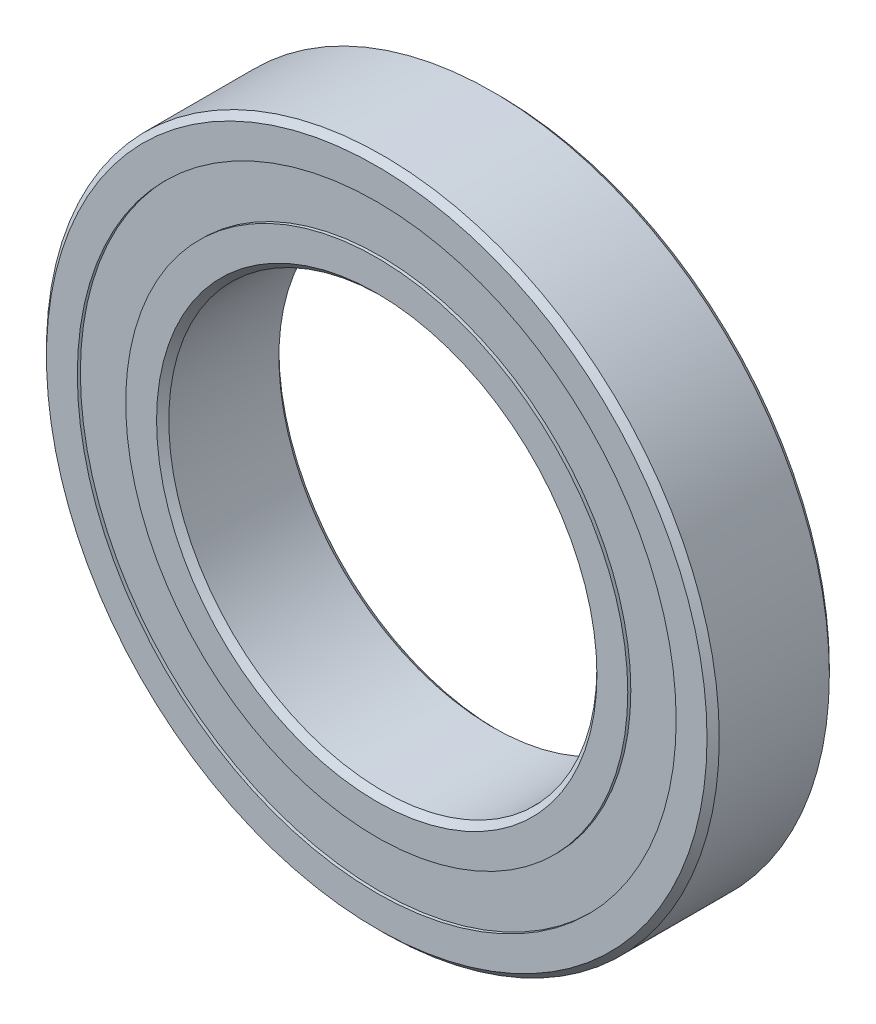
SolidWorks part; units mm, degrees
ref_plane "Front Plane" through (0, 0, 0) normal (0, 0, 1) x (1, 0, 0)
ref_plane "Top Plane" through (0, 0, 0) normal (0, 1, 0) x (1, 0, 0)
ref_plane "Right Plane" through (0, 0, 0) normal (1, 0, 0) x (0, 0, -1)
sketch "Sketch1" plane through (0, 0, 0) normal (1, 0, 0) x (0, 0, -1)
  line L0 (-5, 0) -> (5, 0) construction
  line L1 (0, 27.5) -> (0, -27.5) construction
  line L2 (4.5, 27.5) -> (-4.5, 27.5)
  line L3 (-4.5, 27.5) -> (-5, 27)
  line L4 (-5, 27) -> (-5, 24.4778)
  line L5 (-5, 24.4778) -> (-2.2222, 24.4778)
  line L6 (5, 24.4778) -> (2.2222, 24.4778)
  line L7 (5, 27) -> (5, 24.4778)
  line L8 (4.5, 27.5) -> (5, 27)
  line L9 (0, 27.5) -> (0, 22.4997) construction
  line L10 (0, 22.4997) -> (0, 17.4995) construction
  arc A0 (-2.2222, 24.4778) -> (2.2222, 24.4778) centre (0, 22.4997) cw
  point P14 (0, 17.4995)
  dimension "Width" = 10
  dimension "OD" = 55
  dimension "D1" = 45
  dimension "D2" = 0.5
  dimension "Shaft Dia" = 34.999
  dimension "D3" = 4.4444
  dimension "D4" = 1.978
revolve "Revolve1" add sketch "Sketch1" angle 360 about L0
sketch "Sketch3" plane through (0, 0, 0) normal (1, 0, 0) x (0, 0, -1)
  line L0 (-5, 20.5217) -> (-2.2222, 20.5217)
  line L1 (0, 27.5) -> (0, -27.5) construction
  line L2 (-5, 27) -> (-5, 24.4778) construction
  line L3 (-5, 20.5217) -> (-5, 17.9995)
  line L4 (-4.5, 27.5) -> (-5, 27) construction
  line L5 (-5, 17.9995) -> (-4.5, 17.4995)
  line L6 (-4.5, 17.4995) -> (4.5, 17.4995)
  line L7 (4.5, 27.5) -> (4.5, -27.5) construction
  line L8 (4.5, 17.4995) -> (5, 17.9995)
  line L9 (5, -27) -> (5, 27) construction
  line L10 (5, 17.9995) -> (5, 20.5217)
  line L11 (5, 20.5217) -> (2.2222, 20.5217)
  line L13 (4.5, 27.5) -> (5, 27) construction
  arc A0 (2.2222, 24.4778) -> (-2.2222, 24.4778) centre (0, 22.4997) ccw construction
  arc A1 (2.2222, 20.5217) -> (-2.2222, 20.5217) centre (0, 22.4997) cw
revolve "Revolve3" add sketch "Sketch3" angle 360 about L0
sketch "Sketch4" plane through (0, 0, 0) normal (1, 0, 0) x (0, 0, -1)
  line L0 (-2.975, 22.4997) -> (2.975, 22.4997)
  arc A2 (-2.975, 22.4997) -> (2.975, 22.4997) centre (0, 22.4997) cw
  arc A3 (2.2222, 24.4778) -> (-2.2222, 24.4778) centre (0, 22.4997) ccw construction
revolve "Revolve4" add sketch "Sketch4" angle 360 about L0
ref_axis "Axis1" through (0, 0, -5) along (0, 0, 1)
pattern_circular "CirPattern1" count 12 every 30 about axis through (0, 0, -5) along (0, 0, 1) of bodies 104
sketch "Sketch5" plane through (0, 0, 0) normal (1, 0, 0) x (0, 0, -1)
  line L0 (-5, 24.4778) -> (-2.2222, 24.4778) construction
  line L1 (-4.75, 24.4778) -> (-2.975, 24.4778)
  line L2 (-4.75, 24.4778) -> (-4.75, 20.5217)
  line L3 (-4.75, 20.5217) -> (-2.975, 20.5217)
  line L4 (-2.975, 24.4778) -> (-2.975, 20.5217)
  line L5 (-5, 20.5217) -> (-2.2222, 20.5217) construction
  line L6 (5, 24.4778) -> (2.2222, 24.4778) construction
  line L7 (4.75, 24.4778) -> (2.975, 24.4778)
  line L8 (4.75, 24.4778) -> (4.75, 20.5217)
  line L9 (4.75, 20.5217) -> (2.975, 20.5217)
  line L10 (2.975, 24.4778) -> (2.975, 20.5217)
  line L11 (5, 20.5217) -> (2.2222, 20.5217) construction
  line L12 (-4.5, 27.5) -> (-5, 27) construction
  point P18 (-4.75, 27.25)
revolve "Revolve5" add sketch "Sketch5" angle 360 about L0
equation "\"D2@Sketch1\" = \"Width@Sketch1\"*.05"
equation "\"D3@Sketch1\" = \"Width@Sketch1\"/2.25"
equation "\"D4@Sketch1\" = (((\"OD@Sketch1\"-\"Width@Sketch1\")/2)/3.25)/3.5"
equation "\"D2@CirPattern1\" = 360/\"Balls@CirPattern1\""
